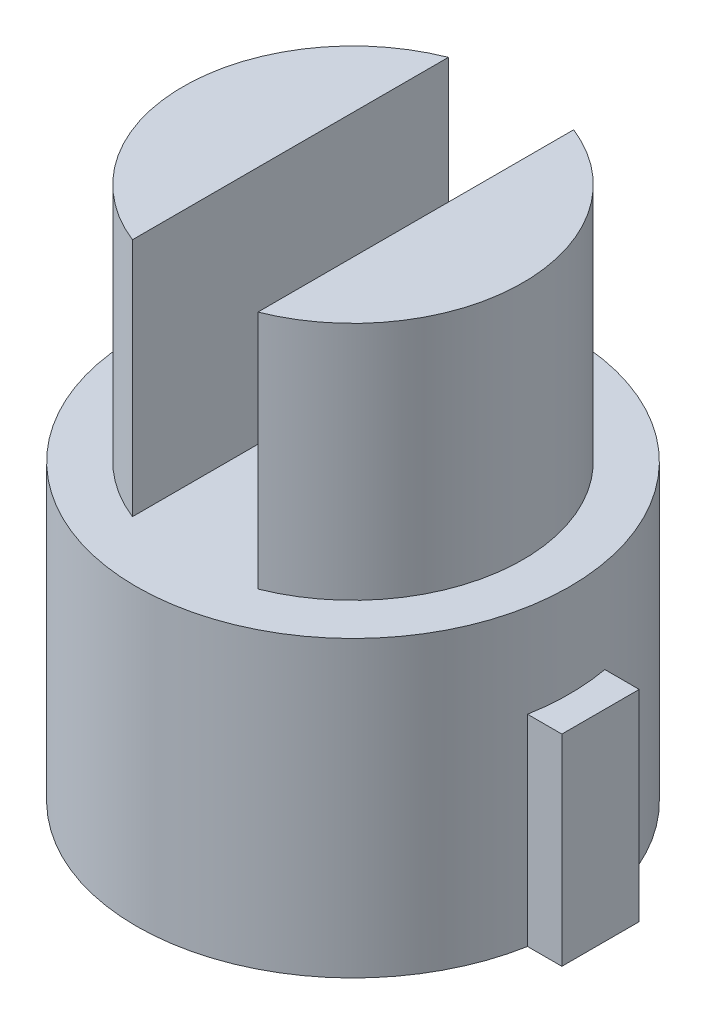
SolidWorks part; units mm, degrees
ref_plane "前视基准面" through (0, 0, 0) normal (0, 0, 1) x (1, 0, 0)
ref_plane "上视基准面" through (0, 0, 0) normal (0, 1, 0) x (1, 0, 0)
ref_plane "右视基准面" through (0, 0, 0) normal (1, 0, 0) x (0, 0, -1)
other "Configuration Table"
sketch "Sketch1" plane through (0, 0, 0) normal (0, 1, 0) x (1, 0, 0)
  line L2 (-4.0485, -10.2142) -> (-4.0458, -10.2074)
  line L3 (0, -2.4982) -> (15.9953, -2.4982)
  line L5 (0, 2.5) -> (15.9953, 2.5)
  line L6 (15.9953, -2.4982) -> (15.9953, 2.5)
  line L7 (0, -2.4982) -> (-16, -2.4982)
  line L9 (0, 2.5018) -> (-16, 2.5018)
  line L10 (-16, -2.4982) -> (-16, 2.5018)
  line L21 (-4.0435, 10.2084) -> (-4.0435, -10.2455)
  line L23 (4.0582, 10.2084) -> (4.0582, -10.2025)
  circle A0 centre (0, 0) radius 10.98
  circle A1 centre (0, 0) radius 14
  dimension "D1" = 4.9982
  dimension "D2" = 15.9953
  dimension "D3" = 5
  dimension "D4" = 16
  dimension "D5" = 20.4539
  dimension "D6" = 8.1017
extrude "Boss-Extrude1" add sketch "Sketch1" along normal blind 34.5 contours L7 A0 L2 | L9 A0 L7 | A0 L9 | L5 A0 | L3 A0 L5 | A0 L3 region at (7.4719, 0, -0.0009) region at (6.6422, 0, 5.4705) region at (-6.6336, 0, 5.4735) region at (-7.4645, 0, -0.0017) region at (6.6419, 0, -5.4716) region at (-6.6331, 0, -5.4755)
extrude "Boss-Extrude2" add sketch "Sketch1<4>" along normal blind 19 contours L5 A1 L9 A0 | L9 A1 L7 A0 | L7 A1 L3 A0 | L3 A1 L5 A0 | L23 A0 L21 L7 L3 | L21 A0 L23 L3 L7 region at (0.0071, 0, -4.1157) region at (0.0069, 0, 6.6151) region at (12.4044, 0, -0.0009) region at (12.2337, 0, 2.7968) region at (-12.4043, 0, -0.0018) region at (8.5462, 0, -7.3599)
sketch "Sketch1<4>" plane through (0, 0, 0) normal (0, 1, 0) x (1, 0, 0) same geometry as "Sketch1"
extrude "Boss-Extrude3" add sketch "Sketch1<5>" along normal blind 13 contours A1 L9 L10 L7 | A1 L3 L6 L5 region at (14.9592, 0, -0.0009) region at (-14.9615, 0, -0.0019)
sketch "Sketch1<5>" plane through (0, 0, 0) normal (0, 1, 0) x (1, 0, 0) same geometry as "Sketch1"
